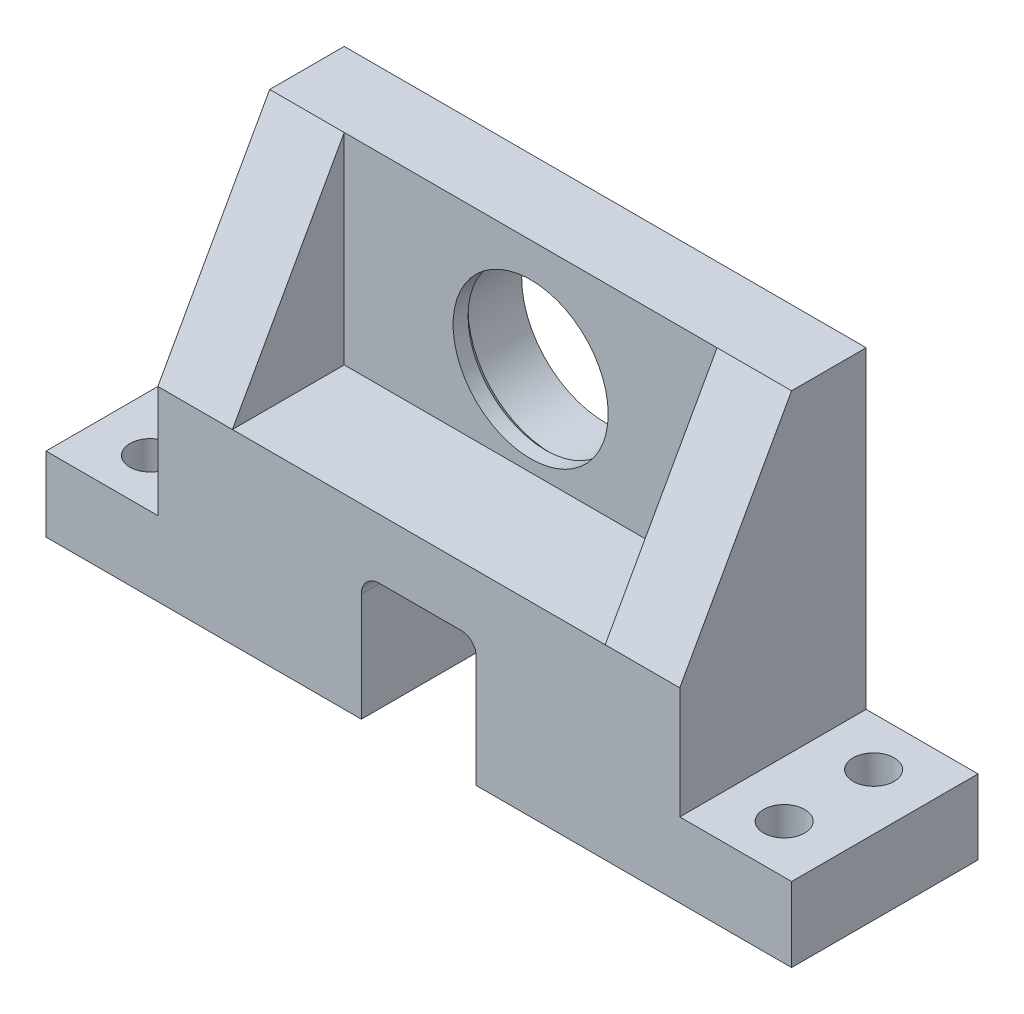
SolidWorks part; units mm, degrees
ref_plane "Front Plane" through (0, 0, 0) normal (0, 0, 1) x (1, 0, 0)
ref_plane "Top Plane" through (0, 0, 0) normal (0, 1, 0) x (1, 0, 0)
ref_plane "Right Plane" through (0, 0, 0) normal (1, 0, 0) x (0, 0, -1)
sketch "Sketch1" plane through (0, 0, 0) normal (0, 0, 1) x (1, 0, 0)
  line L1 (50, 0) -> (50, 10)
  line L2 (50, 10) -> (35, 10)
  line L5 (0, 0) -> (0, 37) construction
  line L12 (-50, 10) -> (-35, 10)
  line L13 (-50, 0) -> (-50, 10)
  line L14 (5.7, 17) -> (-5.2601, 17)
  line L15 (-35, 10) -> (-35, 52)
  line L16 (-35, 52) -> (35, 52)
  line L17 (35, 52) -> (35, 10)
  line L18 (-7.7, 0) -> (-7.7, 14.5601)
  line L19 (7.7, 0) -> (7.7, 15)
  line L20 (-7.7, 0) -> (-50, 0)
  line L21 (7.7, 0) -> (50, 0)
  arc A2 (7.7, 15) -> (5.7, 17) centre (5.7, 15) ccw
  arc A3 (-7.7, 14.5601) -> (-5.2601, 17) centre (-5.2601, 14.5601) cw
  dimension "D1" = 2
  dimension "D2" = 2.4399
  dimension "D3" = 15.4
extrude "Boss-Extrude1" add sketch "Sketch1" along normal blind 25
sketch "Sketch2" plane through (0, 0, 0) normal (0, 0, -1) x (-1, 0, 0)
  circle A0 centre (0, 37) radius 11.2
extrude "Cut-Extrude1" cut sketch "Sketch2" against normal through all
sketch "Sketch4" plane through (0, 10, 0) normal (0, 1, 0) x (1, 0, 0)
  line L0 (-42.5, 0) -> (-42.5, -6.5) construction
  line L3 (-35, 0) -> (-50, 0) construction
  line L4 (-42.5, -25) -> (-42.5, -18.5) construction
  line L5 (-35, -25) -> (-50, -25) construction
  line L6 (42.5, 0) -> (42.5, -6.5) construction
  line L7 (50, 0) -> (35, 0) construction
  line L8 (42.5, -25) -> (42.5, -18.5) construction
  line L9 (50, -25) -> (35, -25) construction
sketch "Sketch11" plane through (0, 0, 25) normal (0, 0, 1) x (1, 0, 0)
  line L1 (-45, 55) -> (45, 55)
  line L2 (-45, 55) -> (-45, 25)
  line L3 (-45, 25) -> (45, 25)
  line L4 (45, 55) -> (45, 25)
  line L5 (-45, 55) -> (45, 25) construction
  line L6 (-45, 25) -> (45, 55) construction
  point P0 (0, 37)
extrude "Cut-Extrude4" cut sketch "Sketch11" against normal blind 15
sketch "Sketch12" plane through (-35, 0, 0) normal (-1, 0, 0) x (0, 0, 1)
  line L0 (10, 52) -> (10, 25)
  line L1 (10, 25) -> (25, 25)
  line L2 (25, 25) -> (10, 52)
extrude "Boss-Extrude2" add sketch "Sketch12" against normal blind 10
sketch "Sketch13" plane through (35, 0, 0) normal (1, 0, 0) x (0, 0, -1)
  line L0 (-10, 52) -> (-10, 25)
  line L1 (-10, 25) -> (-25, 25)
  line L2 (-25, 25) -> (-10, 52)
extrude "Boss-Extrude3" add sketch "Sketch13" against normal blind 10
sketch "Sketch14" plane through (0, 0, 10) normal (0, 0, 1) x (1, 0, 0)
  circle A0 centre (0, 37) radius 11.4
  circle A1 centre (0, 37) radius 10.4
extrude "Boss-Extrude4" add sketch "Sketch14" against normal blind 3
chamfer "Chamfer1" distance 1 angle 45 1 edges at (10.4, 37, 7)
hole_wizard "M5 Clearance Hole1" positions "Sketch15" profile "Sketch16" hole size "M5" standard "ISO" end condition up to next
sketch "Sketch15" plane through (0, 10, 0) normal (0, 1, 0) x (1, 0, 0)
  point P0 (42.5, -18.5)
  point P3 (42.5, -6.5)
  point P6 (-42.5, -18.5)
  point P9 (-42.5, -6.5)
sketch "Sketch16" plane through (42.5, 10, 18.5) normal (1, 0, 0) x (0, 0, 1)
  line L0 (0, 0) -> (0, 10)
  line L1 (0, 10) -> (2.75, 10)
  line L2 (2.75, 10) -> (2.75, 0)
  line L5 (2.75, 0) -> (0, 0)
  line L11 (0, -6.35) -> (0, 107.95) construction
  dimension "Thru Hole Dia." = 5.5
  dimension "Thru Hole Depth" = 10
